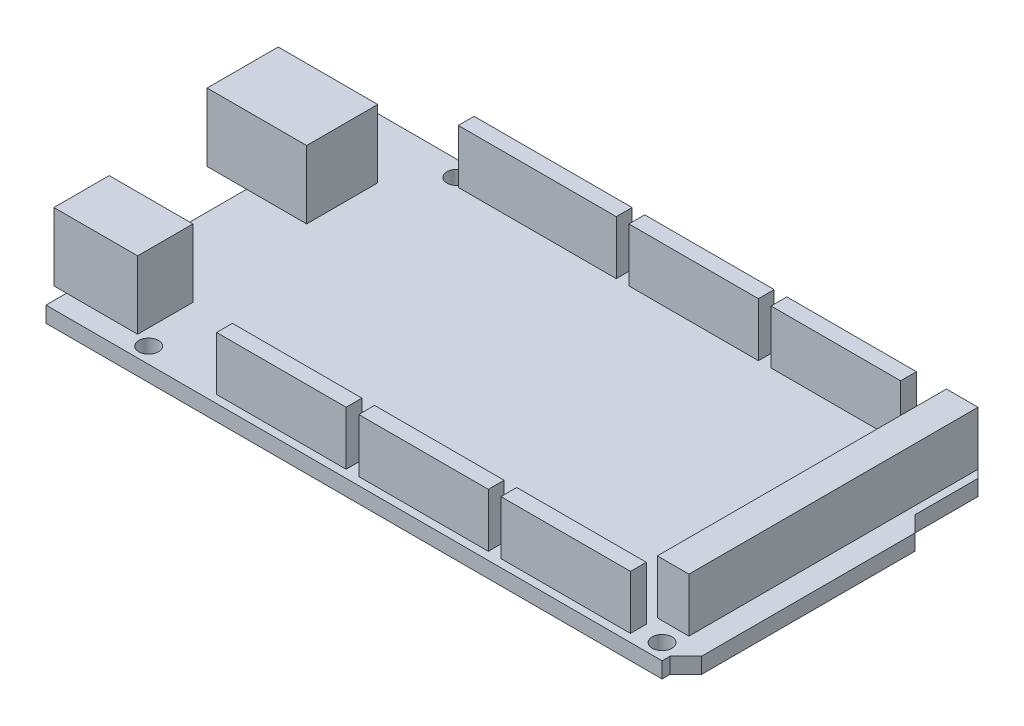
SolidWorks part; units mm, degrees
ref_plane "Front Plane" through (0, 0, 0) normal (0, 0, 1) x (1, 0, 0)
ref_plane "Top Plane" through (0, 0, 0) normal (0, 1, 0) x (1, 0, 0)
ref_plane "Right Plane" through (0, 0, 0) normal (1, 0, 0) x (0, 0, -1)
sketch "Sketch2" plane through (0, 0, 0) normal (0, 1, 0) x (1, 0, 0)
  line L0 (-49.53, 26.67) -> (49.53, 26.67)
  line L1 (49.53, 26.67) -> (49.53, 13.97)
  line L2 (49.53, 13.97) -> (52.07, 13.97)
  line L3 (52.07, 13.97) -> (52.07, -25.4)
  line L4 (52.07, -25.4) -> (49.53, -25.4)
  line L5 (49.53, -25.4) -> (49.53, -26.67)
  line L6 (49.53, -26.67) -> (-49.53, -26.67)
  line L7 (-49.53, -26.67) -> (-49.53, 26.67)
  line L8 (-49.53, 0) -> (52.07, 0) construction
  line L9 (0, 26.67) -> (0, -26.67) construction
  dimension "D1" = 53.34
  dimension "D2" = 2.54
  dimension "D3" = 1.27
  dimension "D4" = 101.6
  dimension "D6" = 12.7
extrude "Boss-Extrude1" add sketch "Sketch2" along normal blind 2.54
sketch "Sketch3" plane through (0, 2.54, 0) normal (0, 1, 0) x (1, 0, 0)
  line L0 (-49.53, 26.67) -> (-49.53, -26.67) construction
  line L1 (49.53, 26.67) -> (-49.53, 26.67) construction
  line L2 (-49.53, -26.67) -> (49.53, -26.67) construction
  circle A0 centre (-34.29, 24.13) radius 1.5875
  circle A1 centre (40.64, 24.13) radius 1.5875
  circle A2 centre (46.99, -24.13) radius 1.5875
  circle A3 centre (-35.56, -24.13) radius 1.5875
  dimension "D7" = 3.175
  dimension "D1" = 15.24
  dimension "D2" = 2.54
  dimension "D3" = 74.93
  dimension "D4" = 2.54
  dimension "D5" = 1.27
  dimension "D6" = 82.55
extrude "Cut-Extrude1" cut sketch "Sketch3" against normal through all
chamfer "Chamfer1" distance 2.54 angle 45 3 edges at (52.07, 1.27, 25.4) (49.53, 1.27, -26.67) (52.07, 1.27, -13.97)
sketch "Sketch4" plane through (0, 2.54, 0) normal (0, 1, 0) x (1, 0, 0)
  line L0 (-49.53, -26.67) -> (49.53, -26.67) construction
  line L1 (-32.766, 25.4) -> (-7.366, 25.4)
  line L2 (-32.766, 25.4) -> (-32.766, 22.86)
  line L3 (-32.766, 22.86) -> (-7.366, 22.86)
  line L4 (-7.366, 25.4) -> (-7.366, 22.86)
  line L5 (-5.334, 25.4) -> (15.494, 25.4)
  line L6 (-5.334, 25.4) -> (-5.334, 22.86)
  line L7 (-5.334, 22.86) -> (15.494, 22.86)
  line L8 (15.494, 25.4) -> (15.494, 22.86)
  line L9 (17.526, 25.4) -> (38.354, 25.4)
  line L10 (17.526, 25.4) -> (17.526, 22.86)
  line L11 (17.526, 22.86) -> (38.354, 22.86)
  line L12 (38.354, 25.4) -> (38.354, 22.86)
  line L13 (43.18, 25.4) -> (48.26, 25.4)
  line L14 (43.18, 25.4) -> (43.18, -21.082)
  line L15 (43.18, -21.082) -> (48.26, -21.082)
  line L16 (48.26, 25.4) -> (48.26, -21.082)
  line L17 (43.18, -25.4) -> (22.352, -25.4)
  line L18 (43.18, -25.4) -> (43.18, -22.86)
  line L19 (43.18, -22.86) -> (22.352, -22.86)
  line L20 (22.352, -25.4) -> (22.352, -22.86)
  line L21 (20.32, -22.86) -> (-0.508, -22.86)
  line L22 (20.32, -22.86) -> (20.32, -25.4)
  line L23 (20.32, -25.4) -> (-0.508, -25.4)
  line L24 (-0.508, -22.86) -> (-0.508, -25.4)
  line L25 (-2.54, -22.86) -> (-23.368, -22.86)
  line L26 (-2.54, -22.86) -> (-2.54, -25.4)
  line L27 (-2.54, -25.4) -> (-23.368, -25.4)
  line L28 (-23.368, -22.86) -> (-23.368, -25.4)
  line L29 (46.99, 26.67) -> (-49.53, 26.67) construction
  line L30 (52.07, -22.86) -> (52.07, 11.43) construction
  dimension "D1" = 1.27
  dimension "D2" = 8.89
  dimension "D3" = 20.828
  dimension "D4" = 2.54
  dimension "D5" = 25.4
  dimension "D6" = 1.27
  dimension "D7" = 13.716
  dimension "D8" = 2.032
  dimension "D9" = 2.032
  dimension "D10" = 2.032
  dimension "D11" = 2.032
  dimension "D12" = 46.482
  dimension "D13" = 5.08
  dimension "D14" = 3.81
  dimension "D15" = 1.27
extrude "Boss-Extrude2" add sketch "Sketch4" along normal blind 8.636 separate body
sketch "Sketch5" plane through (0, 2.54, 0) normal (0, 1, 0) x (1, 0, 0)
  line L0 (-49.53, -26.67) -> (49.53, -26.67) construction
  line L1 (-55.88, 17.018) -> (-39.878, 17.018)
  line L2 (-55.88, 17.018) -> (-55.88, 5.588)
  line L3 (-55.88, 5.588) -> (-39.878, 5.588)
  line L4 (-39.878, 17.018) -> (-39.878, 5.588)
  line L5 (-51.562, -14.478) -> (-38.1, -14.478)
  line L6 (-51.562, -14.478) -> (-51.562, -23.368)
  line L7 (-51.562, -23.368) -> (-38.1, -23.368)
  line L8 (-38.1, -14.478) -> (-38.1, -23.368)
  line L9 (-49.53, 26.67) -> (-49.53, -26.67) construction
  line L10 (46.99, 26.67) -> (-49.53, 26.67) construction
  dimension "D1" = 16.002
  dimension "D2" = 11.43
  dimension "D3" = 8.89
  dimension "D4" = 13.462
  dimension "D5" = 3.302
  dimension "D6" = 2.032
  dimension "D7" = 6.35
  dimension "D8" = 9.652
extrude "Boss-Extrude3" add sketch "Sketch5" along normal blind 10.922 separate body
